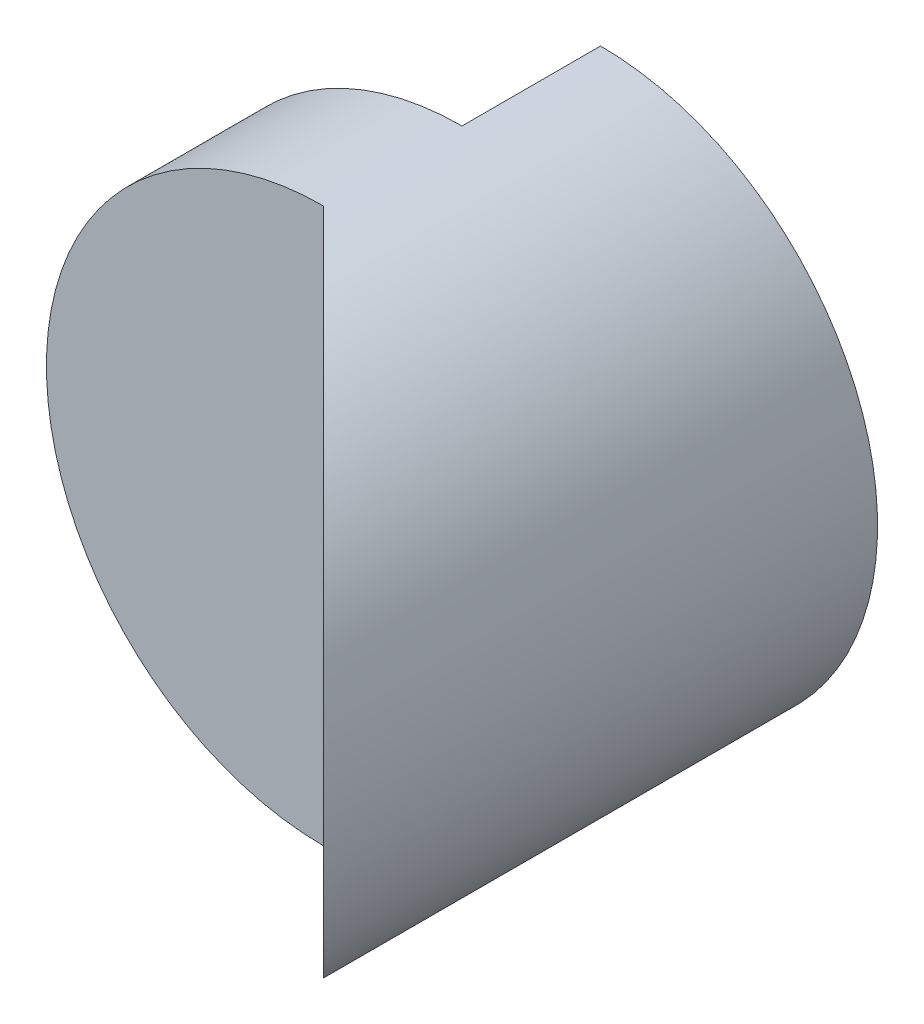
SolidWorks part; units mm, degrees
ref_plane "Front Plane" through (0, 0, 0) normal (0, 0, 1) x (1, 0, 0)
ref_plane "Top Plane" through (0, 0, 0) normal (0, 1, 0) x (1, 0, 0)
ref_plane "Right Plane" through (0, 0, 0) normal (1, 0, 0) x (0, 0, -1)
sketch "Sketch1" plane through (0, 0, 0) normal (0, 0, 1) x (1, 0, 0)
  circle A0 centre (0, 0) radius 20
  dimension "D1" = 40
extrude "Boss-Extrude1" add sketch "Sketch1" along normal blind 40
sketch "Sketch2" plane through (0, 0, 0) normal (0, 1, 0) x (1, 0, 0)
  line L0 (-20, -20) -> (0, -20)
  line L1 (-20, 0) -> (0, 0)
  line L2 (-20, 0) -> (-20, -10)
  line L3 (-20, -10) -> (0, -10)
  line L4 (0, 0) -> (0, -10)
  line L5 (-20, 0) -> (-20, -40) construction
  line L6 (0, -20) -> (20, -40)
  line L7 (-20, -40) -> (20, -40) construction
  line L8 (20, -40) -> (-20, -40)
  line L9 (-20, -40) -> (-20, -20)
  dimension "D1" = 10
  dimension "D2" = 20
  dimension "D3" = 20
  dimension "D4" = 20
  dimension "D5" = 40
extrude "Cut-Extrude2" cut sketch "Sketch2" along normal blind 40 and the other way blind 40
